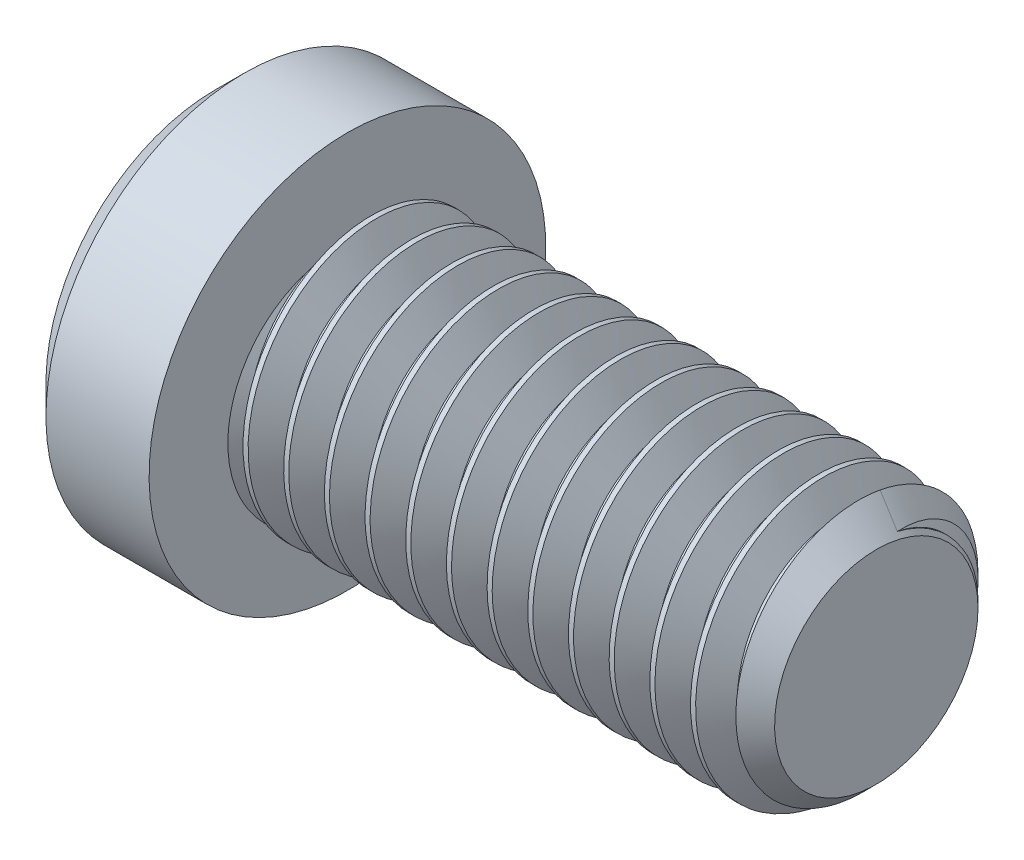
SolidWorks part; units mm, degrees
ref_plane "Front Plane" through (0, 0, 0) normal (0, 0, 1) x (1, 0, 0)
ref_plane "Top Plane" through (0, 0, 0) normal (0, 1, 0) x (1, 0, 0)
ref_plane "Right Plane" through (0, 0, 0) normal (1, 0, 0) x (0, 0, -1)
sketch "Sketch1" plane through (0, 0, 0) normal (0, 0, 1) x (1, 0, 0)
  line L0 (12.7, 0) -> (-12.7, 0) construction
  line L1 (12.7, 6.35) -> (12.7, -6.35) construction
  line L2 (-12.7, 9.525) -> (-12.7, -9.525) construction
  line L3 (-12.7, 9.525) -> (-17.653, 9.525) construction
  line L4 (-17.653, 9.525) -> (-19.05, 8.128) construction
  line L5 (-19.05, 8.128) -> (-19.05, -8.128) construction
  line L6 (-19.05, -8.128) -> (-17.653, -9.525) construction
  line L7 (-17.653, -9.525) -> (-12.7, -9.525) construction
  point P7 (-15.2146, 0)
  point P12 (4.8846, -6.35)
  dimension "D1" = 45
  dimension "Dec." = 12.7
  dimension "Length" = 25.4
  dimension "Head Dia" = 19.05
  dimension "Head Height" = 6.35
  dimension "Hex Depth" = 3.8354
  dimension "Chamfer" = 1.397
  dimension "D2" = 7.8154
ref_plane "Plane1" through (12.7, 0, 0) normal (1, 0, 0) x (0, 0, -1)
ref_plane "Plane2" through (-19.05, 0, 0) normal (1, 0, 0) x (0, 0, -1)
sketch "Sketch2" plane through (12.7, 0, 0) normal (1, 0, 0) x (0, 0, -1)
  circle A0 centre (0, 0) radius 6.35
extrude "Boss-Extrude1" add sketch "Sketch2" against normal up to vertex (25.4 mm away) up to point (-12.7, 0, 0)
sketch "Sketch3" plane through (12.7, 0, 0) normal (1, 0, 0) x (0, 0, -1)
  circle A0 centre (0, 0) radius 6.35 construction
  circle A1 centre (0, 0) radius 6.35
curve "Helix/Spiral1" pitch 1.9538 height 27.3538 radius 6.35 centre (12.7, 0, 0) axis (-1, 0, 0) start towards (0, 1, 0) parameters "Pitch"=1.9538
chamfer "Chamfer1" distance 1.4654 angle 45 1 edges at (12.7, 0, -6.35)
sketch "Sketch5" plane through (0, 0, 0) normal (0, 0, 1) x (1, 0, 0)
  line L0 (11.8452, 6.35) -> (13.5548, 6.35)
  line L1 (13.5548, 6.35) -> (12.8221, 5.0809)
  line L2 (12.8221, 5.0809) -> (12.5779, 5.0809)
  line L3 (12.5779, 5.0809) -> (11.8452, 6.35)
  line L4 (12.7, 5.0809) -> (12.7, 6.35) construction
  line L5 (12.2115, 5.7155) -> (13.1885, 5.7155) construction
  dimension "D1" = 60
  dimension "D2" = 0.9769
  dimension "D3" = 0.2442
sweep "Cut-Sweep1" cut profiles "Sketch5" path "Helix/Spiral1" align with end faces yes
sketch "Sketch4" plane through (-19.05, 0, 0) normal (1, 0, 0) x (0, 0, -1)
  line L0 (-9.525, 0.7937) -> (9.525, 0.7937) construction
  line L1 (0, 3.6662) -> (-3.175, 1.8331)
  line L2 (-3.175, 1.8331) -> (-3.175, -1.8331)
  line L3 (-3.175, -1.8331) -> (0, -3.6662)
  line L4 (0, -3.6662) -> (3.175, -1.8331)
  line L5 (3.175, -1.8331) -> (3.175, 1.8331)
  line L6 (3.175, 1.8331) -> (0, 3.6662)
  line L7 (0, 0) -> (0, 0.7937) construction
  circle A0 centre (0, 0) radius 3.175 construction
  dimension "Hex Size" = 6.35
  dimension "D1" = 19.05
  dimension "D2" = 0.7937
sketch "Sketch6" plane through (0, 0, 0) normal (0, 0, 1) x (1, 0, 0)
  line L0 (-17.653, 9.525) -> (-19.05, 8.128) construction
  line L1 (-12.7, 9.525) -> (-17.653, 9.525) construction
  line L2 (-12.7, 9.525) -> (-12.7, -9.525) construction
  line L3 (-19.05, 8.128) -> (-19.05, -8.128) construction
  line L4 (-17.653, 9.525) -> (-19.05, 8.128)
  line L5 (-12.7, 9.525) -> (-17.653, 9.525)
  line L6 (-12.7, 9.525) -> (-12.7, 0)
  line L7 (-19.05, 8.128) -> (-19.05, 0)
  line L8 (-12.7, 0) -> (-19.05, 0) construction
  line L9 (-12.7, 0) -> (-19.05, 0)
revolve "Revolve1" add sketch "Sketch6" angle 360 about L8
extrude "Cut-Extrude1" cut sketch "Sketch4" along normal up to vertex (3.8354 mm away) up to point (-15.2146, 0, 0)
sketch "Sketch8" plane through (-19.05, 0, 0) normal (-1, 0, 0) x (0, 0, 1)
  circle A1 centre (0, 0) radius 3.6662
extrude "Cut-Extrude2" cut sketch "Sketch8" against normal through all draft 45
equation "\"D3@Helix/Spiral1\" = \"Length@Sketch1\"+\"Pitch@Helix/Spiral1\""
equation "\"D3@Sketch5\" = \"Pitch@Helix/Spiral1\"*.125"
equation "\"D2@Sketch5\" = \"Pitch@Helix/Spiral1\"*.50"
equation "\"D1@Chamfer1\" = \"Pitch@Helix/Spiral1\"*.75"
equation "\"D2@Sketch1\" = \"Pitch@Helix/Spiral1\"*4"
equation "\"D1@Sketch4\" = \"Head Dia@Sketch1\""
